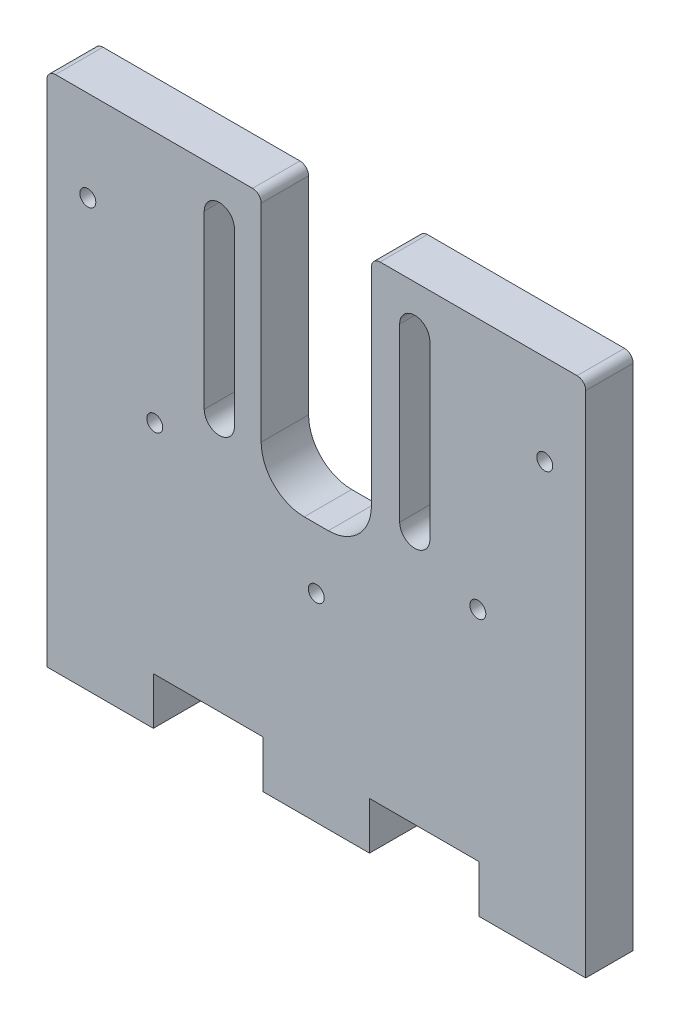
SolidWorks part; units mm, degrees
ref_plane "Front Plane" through (0, 0, 0) normal (0, 0, 1) x (1, 0, 0)
ref_plane "Top Plane" through (0, 0, 0) normal (0, 1, 0) x (1, 0, 0)
ref_plane "Right Plane" through (0, 0, 0) normal (1, 0, 0) x (0, 0, -1)
sketch "Sketch2" plane through (0, 0, 0) normal (0, 0, 1) x (1, 0, 0)
  line L1 (-0.1872, 0) -> (-0.1872, 118)
  line L9 (1.8128, 120) -> (47.5254, 120)
  line L10 (49.5254, 118) -> (49.5254, 70)
  line L11 (59.5254, 60) -> (65.1001, 60)
  line L12 (75.1001, 70) -> (75.1001, 118)
  line L13 (77.1001, 120) -> (122.8128, 120)
  line L14 (124.8128, 118) -> (124.8128, 0)
  line L16 (39.8128, 70) -> (39.8128, 109.8096) construction
  line L17 (36.3128, 70) -> (36.3128, 109.8096)
  line L18 (43.3128, 70) -> (43.3128, 109.8096)
  line L19 (-0.1872, 0) -> (24.5128, 0)
  line L20 (85.1566, 70) -> (85.1566, 109.8096) construction
  line L21 (88.6566, 70) -> (88.6566, 109.8096)
  line L22 (81.6566, 70) -> (81.6566, 109.8096)
  line L23 (24.5128, 0) -> (24.5128, 11)
  line L24 (24.5128, 11) -> (49.9628, 11)
  line L25 (49.9628, 11) -> (49.9628, 0)
  line L26 (49.9628, 0) -> (74.6628, 0)
  line L27 (74.6628, 0) -> (74.6628, 11)
  line L28 (74.6628, 11) -> (100.1128, 11)
  line L29 (100.1128, 11) -> (100.1128, 0)
  line L30 (100.1128, 0) -> (124.8128, 0)
  line L32 (49.5254, 60) -> (75.1001, 60) construction
  line L33 (49.5254, 60) -> (49.5254, 138) construction
  line L34 (49.5254, 138) -> (75.1001, 138) construction
  line L35 (75.1001, 60) -> (75.1001, 138) construction
  line L36 (49.5254, 60) -> (75.1001, 138) construction
  line L37 (49.5254, 138) -> (75.1001, 60) construction
  arc A6 (59.5254, 60) -> (49.5254, 70) centre (59.5254, 70) cw
  arc A7 (65.1001, 60) -> (75.1001, 70) centre (65.1001, 70) ccw
  arc A8 (49.5254, 118) -> (47.5254, 120) centre (47.5254, 118) ccw
  arc A9 (77.1001, 120) -> (75.1001, 118) centre (77.1001, 118) ccw
  arc A10 (1.8128, 120) -> (-0.1872, 118) centre (1.8128, 118) ccw
  arc A11 (124.8128, 118) -> (122.8128, 120) centre (122.8128, 118) ccw
  arc A14 (36.3128, 70) -> (43.3128, 70) centre (39.8128, 70) ccw
  arc A15 (43.3128, 109.8096) -> (36.3128, 109.8096) centre (39.8128, 109.8096) ccw
  arc A16 (88.6566, 70) -> (81.6566, 70) centre (85.1566, 70) cw
  arc A17 (81.6566, 109.8096) -> (88.6566, 109.8096) centre (85.1566, 109.8096) cw
  circle A23 centre (62.3128, 99) radius 53 construction
  circle A24 centre (62.3128, 46) radius 1.85
  circle A25 centre (24.8361, 61.5233) radius 1.85
  circle A26 centre (9.3128, 99) radius 1.85
  circle A27 centre (24.8361, 136.4767) radius 1.85 [skipped]
  circle A28 centre (62.3128, 152) radius 1.85 [skipped]
  circle A29 centre (99.7894, 136.4767) radius 1.85 [skipped]
  circle A30 centre (115.3128, 99) radius 1.85
  circle A31 centre (99.7894, 61.5233) radius 1.85
  point P23 (49.5254, 94)
  point P24 (39.8128, 89.9048)
  point P32 (85.1566, 89.9048)
  point P45 (62.3128, 99)
  point P50 (0, 0)
  point P51 (0, 0)
  point P52 (0, 0)
  point P69 (62.3128, 99)
  point P70 (39.8128, 75.2469)
  point P71 (0, 0)
  point P72 (0, 0)
  point P73 (0, 0)
  point P74 (0, 0)
  point P75 (0, 0)
  point P76 (0, 0)
  point P77 (0, 0)
  point P78 (0, 0)
  point P79 (0, 0)
  point P80 (0, 0)
  point P81 (0, 0)
  point P82 (84.8128, 73.636)
  point P83 (0, 0)
  point P84 (85.1566, 70)
  dimension "D1" = 125
  dimension "D2" = 120
  dimension "D3" = 2
  dimension "D4" = 2
  dimension "D5" = 2
  dimension "D6" = 2
  dimension "D8" = 106
  dimension "D7" = 11
  dimension "D9" = 3.7
  dimension "D10" = 8
  dimension "D11" = 24.7
extrude "Boss-Extrude7" add sketch "Sketch2" along normal blind 11
